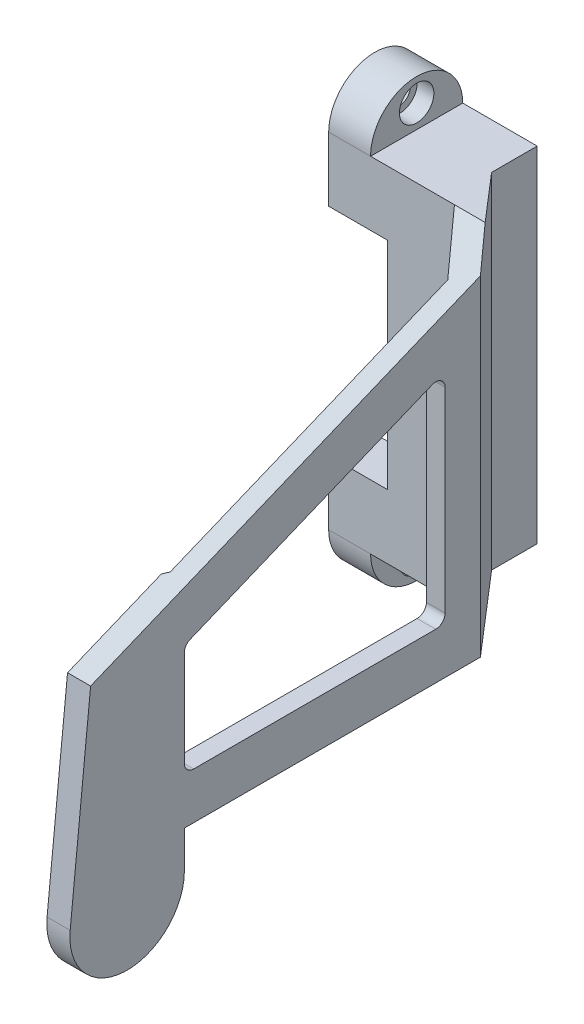
SolidWorks part; units mm, degrees
ref_plane "Płaszczyzna przednia" through (0, 0, 0) normal (0, 0, 1) x (1, 0, 0)
ref_plane "Płaszczyzna górna" through (0, 0, 0) normal (0, 1, 0) x (1, 0, 0)
ref_plane "Płaszczyzna prawa" through (0, 0, 0) normal (1, 0, 0) x (0, 0, -1)
sketch "Szkic1" plane through (0, 0, 0) normal (1, 0, 0) x (0, 0, -1)
  line L0 (0, 0) -> (0, 37)
  line L1 (0, 37) -> (-9.9, 37)
  line L2 (-9.9, 37) -> (-9.9, 0)
  line L3 (-9.9, 0) -> (0, 0)
  dimension "D1" = 37
  dimension "D2" = 9.9
extrude "Dodanie-wyciągnięcie1" add sketch "Szkic1" along normal blind 12.5
sketch "Szkic2" plane through (12.5, 0, 0) normal (1, 0, 0) x (0, 0, -1)
  line L0 (-9.9, 37) -> (-7.4, 37)
  line L1 (-51.55, 12.25) -> (-51.55, -4) construction
  line L2 (-45.4, 0) -> (-7.4, 0)
  line L3 (-9.9, 37) -> (-55.4724, 18.25)
  line L4 (-7.4, 0) -> (-7.4, 37)
  line L5 (-9.9, 37) -> (-9.9, 0) construction
  line L6 (-53.55, 12.25) -> (-55.2, -4) construction
  line L8 (-45.4, 0) -> (-45.4, -4)
  line L10 (-55.4724, 18.25) -> (-57.6685, -3.3787)
  line L12 (-9.9, 0) -> (0, 0)
  line L13 (0, 0) -> (0, 37)
  line L14 (0, 37) -> (-9.9, 37)
  line L15 (-9.9, 37) -> (-9.9, 0)
  line L16 (-9.9, 0) -> (0, 0)
  line L17 (0, 0) -> (0, 37)
  line L18 (0, 37) -> (-9.9, 37)
  line L19 (-9.9, 37) -> (-9.9, 0)
  arc A3 (-45.4, -4) -> (-57.6685, -3.3787) centre (-51.55, -4) cw
  circle A4 centre (-51.55, -4) radius 3.65
  circle A5 centre (-51.55, 12.25) radius 2
  point P2 (-51.55, -7.65)
  point P5 (-51.55, 14.25)
  point P7 (-55.2, -4)
  point P9 (-53.55, 12.25)
  line M5 (-9.9, 0) -> (0, 0)
  line M7 (0, 37) -> (-9.9, 37)
  line M8 (-9.9, 37) -> (-9.9, 0)
  dimension "D3" = 18.75
  dimension "D5" = 2.5
  dimension "D1" = 7.3
  dimension "D2" = 21.9
  dimension "D4" = 2.5
  dimension "D8" = 4
  dimension "D6" = 38
  dimension "D7" = 4
  dimension "D10" = 37
  dimension "D9" = 0
extrude "Dodanie-wyciągnięcie2" add sketch "Szkic2" along normal blind 7.5 contours M8 | M7 M8 M5 | A5 | A4 region at (12.5, 13.3018, 31.2988) region at (12.5, 18.5, 8.65) region at (12.5, -4, 51.55) region at (12.5, 12.25, 51.55)
sketch "Szkic3" plane through (0, 37, 0) normal (0, 1, 0) x (1, 0, 0)
  line L0 (12.5, -55.4724) -> (12.5, -57.6685) construction
  line L1 (12.5, -9.9) -> (13.9645, -9.9)
  line L2 (12.5, -57.6685) -> (20, -57.6685) construction
  line L4 (20, -57.6685) -> (20, -55.4724) construction
  line L5 (12.5, -9.9) -> (12.5, -55.4724) construction
  line L6 (20, -55.4724) -> (20, -9.9) construction
  line L7 (17.5197, -13.4553) -> (0, -13.4553)
  line L8 (0, 0) -> (0, -9.9) construction
  line L9 (0, -9.9) -> (12.5, -9.9) construction
  line L10 (20, -9.9) -> (20, -7.4) construction
  line L11 (20, -7.4) -> (12.5, -7.4) construction
  line L12 (12.5, -7.4) -> (12.5, 0) construction
  line L13 (12.5, 0) -> (0, 0) construction
  line L14 (12.5, -55.4724) -> (12.5, -57.6685)
  line L15 (12.5, -57.6685) -> (20, -57.6685)
  line L16 (20, -57.6685) -> (20, -55.4724)
  line L17 (12.5, -9.9) -> (12.5, -55.4724)
  line L18 (20, -55.4724) -> (20, -9.9)
  line L19 (0, 0) -> (0, -9.9)
  line L20 (0, -9.9) -> (12.5, -9.9)
  line L21 (20, -9.9) -> (20, -7.4)
  line L22 (20, -7.4) -> (12.5, -7.4)
  line L23 (12.5, -7.4) -> (12.5, 0)
  line L24 (12.5, 0) -> (0, 0)
  line L25 (15, -7.4) -> (20, -12.4)
  line L26 (12.5, -9.9) -> (13.9645, -9.9)
  line L27 (20, -9.9) -> (12.5, -9.9) construction
  line L28 (13.9645, -9.9) -> (17.5197, -13.4553)
  line L29 (17.5197, -13.4553) -> (17.5197, -57.6685)
  line L30 (17.5197, -13.4553) -> (17.5197, -62.6685)
  line L31 (17.5197, -62.6685) -> (0, -62.6685)
  line L32 (0, -13.4553) -> (0, -62.6685)
  point P2 (17.5, -9.9)
  line M20 (12.5, -9.9) -> (20, -9.9)
  line M21 (20, -9.9) -> (20, -7.4)
  line M22 (20, -7.4) -> (12.5, -7.4)
  dimension "D1" = 2.4803
  dimension "D2" = 2.5
  dimension "D3" = 45
  dimension "D4" = 2.5
  dimension "D5" = 5
extrude "Wytnij-wyciągnięcie1" cut sketch "Szkic3" against normal through all contours L25 M22 M20 M21 | L25 L18 M20 | L29 L28 L17 L14 L15 M20 | L7 L32 L31 L30 L15 L14 L17 region at (6.5934, 37, 38.9285) region at (15.0099, 37, 35.5619) region at (19.1667, 37, 10.7333) region at (18.0556, 37, 8.5111)
sketch "Szkic4" plane through (0, 0, 9.9) normal (0, 0, 1) x (1, 0, 0)
  line L0 (0, 30.1) -> (6.3, 30.1)
  line L1 (0, 37) -> (0, 0) construction
  line L2 (6.3, 30.1) -> (6.3, 6.9)
  line L3 (6.3, 6.9) -> (0, 6.9)
  line L4 (0, 6.9) -> (0, 30.1)
  point P4 (0, 18.5)
  point P7 (6.3, 18.5)
  point P9 (0, 18.5)
  dimension "D2" = 23.2
  dimension "D3" = 6.3
extrude "Wytnij-wyciągnięcie2" cut sketch "Szkic4" against normal blind 57.5
sketch "Esquisse2" plane through (20, 0, 0) normal (1, 0, 0) x (0, 0, -1)
  arc A0 (-57.6685, -3.3787) -> (-45.4, -4) centre (-51.55, -4) ccw construction
  arc A1 (-57.6685, -3.3787) -> (-45.4, -4) centre (-51.55, -4) ccw
  circle A2 centre (-51.55, -4) radius 1.8
  dimension "D1" = 3.6
extrude "Boss.-Extru.1" add sketch "Esquisse2" against normal blind 3 from surface contours A2 region at (20, -4, 51.55) starting at face at (17.5197, 6.6593, 38.5297)
sketch "Esquisse3" plane through (20, 0, 0) normal (1, 0, 0) x (0, 0, -1)
  line L0 (-17.4, 6) -> (-17.4, 27.0148)
  line L1 (-18.7805, 27.9396) -> (-44.7805, 17.2423)
  line L2 (-44.4, 5) -> (-18.4, 5)
  line L3 (-45.4, 16.3176) -> (-45.4, 6)
  line L4 (-12.4, 35.9714) -> (-55.4724, 18.25) construction
  line L5 (-12.4, 35.9714) -> (-12.4, 0) construction
  line L6 (-45.4, 0) -> (-12.4, 0) construction
  line L7 (-45.4, 0) -> (-45.4, -4) construction
  arc A0 (-17.4, 6) -> (-18.4, 5) centre (-18.4, 6) cw
  arc A1 (-44.4, 5) -> (-45.4, 6) centre (-44.4, 6) cw
  arc A2 (-45.4, 16.3176) -> (-44.7805, 17.2423) centre (-44.4, 16.3176) cw
  arc A3 (-18.7805, 27.9396) -> (-17.4, 27.0148) centre (-18.4, 27.0148) cw
  dimension "D1" = 1
  dimension "D2" = 5
  dimension "D3" = 5
  dimension "D4" = 5
extrude "Enlèv. mat.-Extru.1" cut sketch "Esquisse3" against normal through all contours L0 A3 L1 A2 L3 A1 L2 A0
sketch "Esquisse4" plane through (0, 0, 0) normal (-1, 0, 0) x (0, 0, 1)
  line L0 (9.9, 0) -> (9.9, 6.9) construction
  line L1 (9.9, 6.9) -> (0, 6.9) construction
  line L2 (0, 6.9) -> (0, 0) construction
  line L3 (0, 0) -> (9.9, 0) construction
  line L4 (0, 37) -> (0, 30.1) construction
  line L5 (0, 30.1) -> (9.9, 30.1) construction
  line L6 (9.9, 30.1) -> (9.9, 37) construction
  line L7 (9.9, 37) -> (0, 37) construction
  line L8 (9.9, 0) -> (9.9, 6.9)
  line L9 (9.9, 6.9) -> (0, 6.9)
  line L10 (0, 6.9) -> (0, 0)
  line L11 (0, 0) -> (9.9, 0)
  line L12 (0, 37) -> (0, 30.1)
  line L13 (0, 30.1) -> (9.9, 30.1)
  line L14 (9.9, 30.1) -> (9.9, 37)
  line L15 (9.9, 37) -> (0, 37)
  line L16 (9.9, 18.5) -> (0, 18.5) construction
  line L17 (2.5, 30.1) -> (5.4, 30.1)
  line L18 (2.5, 30.1) -> (2.5, 35.2)
  line L19 (2.5, 35.2) -> (5.4, 35.2)
  line L20 (5.4, 30.1) -> (5.4, 35.2)
  line L21 (9.9, 6.9) -> (9.9, 30.1) construction
  line L22 (0, 6.9) -> (0, 30.1) construction
  line L23 (2.5, 1.8) -> (5.4, 1.8)
  line L24 (5.4, 6.9) -> (5.4, 1.8)
  line L25 (2.5, 6.9) -> (5.4, 6.9)
  line L26 (2.5, 6.9) -> (2.5, 1.8)
  dimension "D1" = 2.9
  dimension "D2" = 2.5
  dimension "D3" = 5.1
extrude "Enlèv. mat.-Extru.2" cut sketch "Esquisse4" against normal up to surface (6.3 mm away) contours L13 L20 L19 L18 | L9 L26 L23 L24 region at (0, 4.35, 3.95) region at (0, 32.65, 3.95) up to face at (6.3, 18.5, 4.95)
sketch "Esquisse5" plane through (0, 0, 0) normal (0, -1, 0) x (1, 0, 0)
  line L0 (15, 7.4) -> (12.5, 4.9)
  line L10 (17.5197, 45.4) -> (17.5197, 13.4553)
  line L11 (17.5197, 13.4553) -> (12.5, 13.4553)
  line L12 (12.5, 9.9) -> (0, 9.9)
  line L13 (0, 9.9) -> (0, 0)
  line L14 (0, 0) -> (12.5, 0)
  line L15 (12.5, 0) -> (12.5, 7.4)
  line L16 (12.5, 7.4) -> (15, 7.4)
  line L17 (15, 7.4) -> (20, 12.4)
  line L18 (20, 12.4) -> (20, 45.4)
  line L19 (20, 45.4) -> (17.5197, 45.4)
  line L20 (17.5197, 45.4) -> (17.5197, 13.4553)
  line L22 (12.5, 9.9) -> (0, 9.9)
  line L23 (0, 9.9) -> (0, 0)
  line L24 (0, 0) -> (12.5, 0)
  line L25 (12.5, 0) -> (12.5, 7.4)
  line L26 (12.5, 7.4) -> (15, 7.4)
  line L27 (15, 7.4) -> (20, 12.4)
  line L28 (20, 12.4) -> (20, 45.4)
  line L29 (20, 45.4) -> (17.5197, 45.4)
  line L32 (17.5197, 13.4553) -> (12.5, 13.4553)
  line L33 (12.5, 13.4553) -> (12.5, 9.9)
  line L34 (12.5, 13.4553) -> (12.5, 9.9)
  line M17 (12.5, 0) -> (12.5, 7.4)
  line M18 (12.5, 7.4) -> (15, 7.4)
  dimension "D1" = 0
extrude "Boss.-Extru.2" add sketch "Esquisse5" against normal up to surface (37 mm away) contours L0 M18 M17 region at (13.3333, 0, 6.5667) up to face at (10.1786, 37, 5.8286)
sketch "Esquisse6" plane through (0, 0, 0) normal (-1, 0, 0) x (0, 0, 1)
  line L0 (0, 18.5) -> (9.9, 18.5) construction
  line L3 (4.95, 41.95) -> (4.95, 37) construction
  line L4 (0, 6.9) -> (0, 30.1) construction
  line L6 (9.9, 6.9) -> (9.9, 30.1) construction
  line L7 (4.95, -4.95) -> (4.95, 0) construction
  line L8 (2.5, 35.2) -> (5.4, 35.2)
  line L9 (5.4, 35.2) -> (5.4, 30.1)
  line L10 (5.4, 30.1) -> (9.9, 30.1)
  line L11 (9.9, 30.1) -> (9.9, 37)
  line L12 (9.9, 37) -> (0, 37)
  line L13 (0, 37) -> (0, 30.1)
  line L14 (0, 30.1) -> (2.5, 30.1)
  line L15 (2.5, 30.1) -> (2.5, 35.2)
  line L20 (9.9, 37) -> (0, 37)
  line L21 (9.9, 0) -> (0, 0)
  circle A0 centre (4.95, 39.475) radius 1.1
  arc A2 (9.9, 37) -> (0, 37) centre (4.95, 37) ccw
  arc A5 (9.9, 0) -> (0, 0) centre (4.95, 0) cw
  circle A6 centre (4.95, -2.475) radius 1.1
  point P19 (4.95, 39.475)
  line M17 (9.9, 37) -> (0, 37)
  dimension "D2" = 2.2
  dimension "D1" = 0
extrude "Boss.-Extru.3" add sketch "Esquisse6" against normal blind 4.5 contours A2 A0 M17 | A5 L21 A6 region at (0, 41.8393, 4.95) region at (0, -4.8393, 4.95)
sketch "Esquisse8" plane through (4.5, 0, 0) normal (1, 0, 0) x (0, 0, -1)
  circle A0 centre (-4.95, -2.475) radius 1.1 construction
  circle A1 centre (-4.95, 39.475) radius 1.1 construction
  circle A2 centre (-4.95, -2.475) radius 1.1
  circle A3 centre (-4.95, 39.475) radius 1.1
  circle A4 centre (-4.95, 39.475) radius 1.85
  circle A5 centre (-4.95, -2.475) radius 1.85
  dimension "D1" = 3.7
extrude "Enlèv. mat.-Extru.5" cut sketch "Esquisse8" against normal blind 1.8
sketch "Esquisse10" plane through (0, 0, 0) normal (0, -1, 0) x (1, 0, 0)
  line L0 (20, 12.4) -> (20, 0)
  line L1 (20, 0) -> (12.5, 0)
  line L2 (12.5, 13.4553) -> (17.5197, 18.475)
  line L10 (4.5, 9.9) -> (4.5, 0)
  line L11 (4.5, 0) -> (12.5, 0)
  line L12 (12.5, 0) -> (12.5, 4.9)
  line L13 (12.5, 4.9) -> (20, 12.4)
  line L14 (20, 12.4) -> (20, 45.4)
  line L15 (20, 45.4) -> (17.5197, 45.4)
  line L16 (17.5197, 45.4) -> (17.5197, 13.4553)
  line L17 (17.5197, 13.4553) -> (12.5, 13.4553)
  line L18 (12.5, 13.4553) -> (12.5, 9.9)
  line L19 (12.5, 9.9) -> (4.5, 9.9)
  line L20 (4.5, 9.9) -> (4.5, 0)
  line L21 (4.5, 0) -> (12.5, 0)
  line L22 (12.5, 0) -> (12.5, 4.9)
  line L23 (12.5, 4.9) -> (20, 12.4)
  line L24 (20, 12.4) -> (20, 45.4)
  line L25 (20, 45.4) -> (17.5197, 45.4)
  line L26 (17.5197, 45.4) -> (17.5197, 13.4553)
  line L27 (17.5197, 13.4553) -> (12.5, 13.4553)
  line L28 (12.5, 13.4553) -> (12.5, 9.9)
  line L29 (12.5, 9.9) -> (4.5, 9.9)
  line M13 (12.5, 0) -> (12.5, 4.9)
  line M14 (12.5, 4.9) -> (20, 12.4)
  line M17 (17.5197, 45.4) -> (17.5197, 13.4553)
  line M18 (17.5197, 13.4553) -> (12.5, 13.4553)
  dimension "D1" = 0
extrude "Boss.-Extru.4" add sketch "Esquisse10" against normal up to surface (37 mm away) contours L1 L0 M14 M13 | L2 M18 M17 region at (16.7919, 0, 4.596) region at (15.8465, 0, 15.1285) up to face at (10.6667, 37, 5.3583)
sketch "Esquisse11" plane through (0, 0, 0) normal (0, -1, 0) x (1, 0, 0)
  line L0 (12.5, 0) -> (12.5, 4.9)
  line L1 (12.5, 4.9) -> (20, 13.6)
  line L2 (12.5, 9.9) -> (13.5096, 9.9)
  line L3 (13.5096, 9.9) -> (20, 17.4288)
  line L4 (17.5197, 18.475) -> (17.5197, 14.5517)
  line L5 (17.5197, 45.4) -> (18, 44.9197)
  line L6 (18, 44.9197) -> (18, 15.1088)
  line L7 (17.5197, 18.475) -> (18, 18.9553) construction
  line L8 (4.5, 0) -> (20, 0)
  line L9 (20, 0) -> (20, 45.4)
  line L10 (20, 45.4) -> (17.5197, 45.4)
  line L11 (17.5197, 45.4) -> (17.5197, 18.475)
  line L12 (17.5197, 18.475) -> (12.5, 13.4553)
  line L13 (12.5, 13.4553) -> (12.5, 9.9)
  line L14 (12.5, 9.9) -> (4.5, 9.9)
  line L15 (4.5, 9.9) -> (4.5, 0)
  line L16 (4.5, 0) -> (20, 0)
  line L17 (20, 0) -> (20, 45.4)
  line L18 (20, 45.4) -> (17.5197, 45.4)
  line L19 (17.5197, 45.4) -> (17.5197, 18.475)
  line L21 (12.5, 13.4553) -> (12.5, 9.9)
  line L22 (12.5, 9.9) -> (4.5, 9.9)
  line L23 (4.5, 9.9) -> (4.5, 0)
  line L26 (17.5197, 18.475) -> (12.5, 13.4553)
  line M10 (4.5, 0) -> (20, 0)
  line M11 (20, 0) -> (20, 45.4)
  line M13 (17.5197, 45.4) -> (17.5197, 18.475)
  line M15 (12.5, 13.4553) -> (12.5, 9.9)
  line M18 (17.5197, 18.475) -> (12.5, 13.4553)
  dimension "D2" = 4.9
  dimension "D3" = 13.6
  dimension "D4" = 2.5
  dimension "D5" = 2
  dimension "D1" = 0
extrude "Enlèv. mat.-Extru.7" cut sketch "Esquisse11" against normal through all contours L7 L6 L5 M13 | L4 L2 L3 M18 M15 | L7 L4 L3 L6 | L1 L0 M10 M11 region at (16.8378, 0, 4.9659) region at (14.9909, 0, 13.8367) region at (17.7591, 0, 16.7719) region at (17.7584, 0, 31.9375)
sketch "Esquisse12" plane through (0, 35.127, 14.4524) normal (0, 0.9248, 0.3805) x (1, 0, 0)
  line L0 (16.5745, 1.0782) -> (17.5197, -0.1074)
  line L11 (20, 0.9217) -> (16.8103, 4.9227)
  line L12 (16.8103, 4.9227) -> (13.5096, 4.9227)
  line L13 (13.5096, 4.9227) -> (16.5745, 1.0782)
  line L14 (16.5745, 1.0782) -> (17.5197, 1.0782)
  line L15 (17.5197, 1.0782) -> (17.5197, -0.1074)
  line L16 (17.5197, -0.1074) -> (18, -0.7098)
  line L17 (18, -0.7098) -> (18, -32.9453)
  line L18 (18, -32.9453) -> (17.5197, -33.4646)
  line L19 (17.5197, -33.4646) -> (17.5197, -44.3562)
  line L20 (17.5197, -44.3562) -> (20, -44.3562)
  line L21 (20, -44.3562) -> (20, 0.9217)
  line L22 (20, 0.9217) -> (16.8103, 4.9227)
  line L23 (16.8103, 4.9227) -> (13.5096, 4.9227)
  line L24 (13.5096, 4.9227) -> (16.5745, 1.0782)
  line L25 (16.5745, 1.0782) -> (17.5197, 1.0782)
  line L26 (17.5197, 1.0782) -> (17.5197, -0.1074)
  line L27 (17.5197, -0.1074) -> (18, -0.7098)
  line L28 (18, -0.7098) -> (18, -32.9453)
  line L29 (18, -32.9453) -> (17.5197, -33.4646)
  line L30 (17.5197, -33.4646) -> (17.5197, -44.3562)
  line L31 (17.5197, -44.3562) -> (20, -44.3562)
  line L32 (20, -44.3562) -> (20, 0.9217)
  line M12 (20, 0.9217) -> (16.8103, 4.9227)
  line M13 (16.8103, 4.9227) -> (13.5096, 4.9227)
  line M14 (13.5096, 4.9227) -> (16.5745, 1.0782)
  line M15 (16.5745, 1.0782) -> (17.5197, 1.0782)
  line M16 (17.5197, 1.0782) -> (17.5197, -0.1074)
  line M17 (17.5197, -0.1074) -> (18, -0.7098)
  line M18 (18, -0.7098) -> (18, -32.9453)
  line M19 (18, -32.9453) -> (17.5197, -33.4646)
  line M20 (17.5197, -33.4646) -> (17.5197, -44.3562)
  line M21 (17.5197, -44.3562) -> (20, -44.3562)
  line M22 (20, -44.3562) -> (20, 0.9217)
  dimension "D1" = 0
extrude "Enlèv. mat.-Extru.8" cut sketch "Esquisse12" along normal through all contours M22 M12 M13 M14 M15 M16 M17 M18 M19 M20 M21 | L0 M15 M16 region at (17.2047, 35.3869, 13.8208) region at (18.6643, 27.7139, 32.4701)
